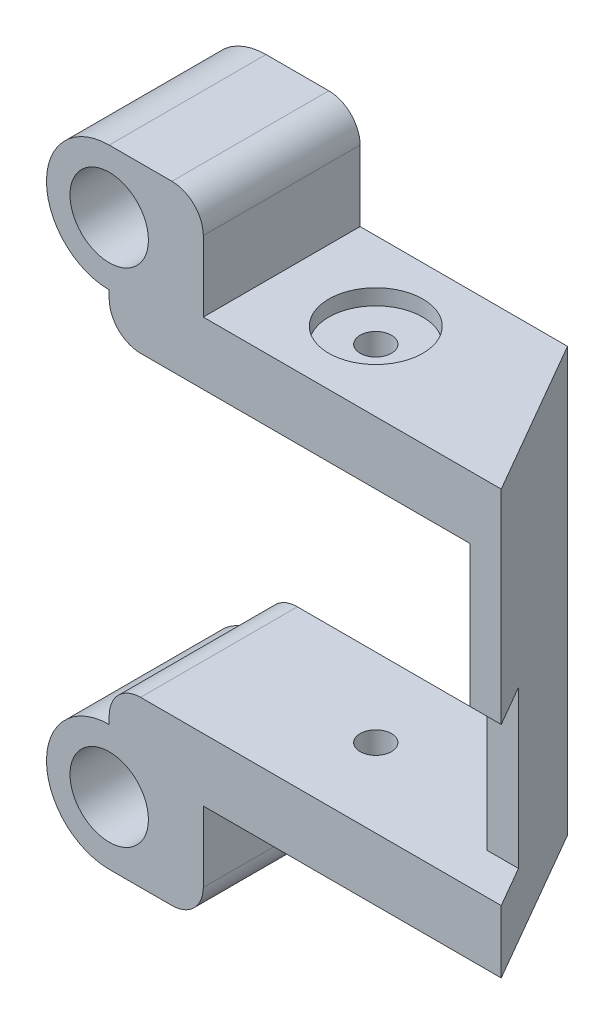
SolidWorks part; units mm, degrees
ref_plane "Alzado" through (0, 0, 0) normal (0, 0, 1) x (1, 0, 0)
ref_plane "Planta" through (0, 0, 0) normal (0, 1, 0) x (1, 0, 0)
ref_plane "Vista lateral" through (0, 0, 0) normal (1, 0, 0) x (0, 0, -1)
sketch "Croquis1" plane through (0, 0, 0) normal (0, 0, 1) x (1, 0, 0)
  line L5 (-106.2316, 22.7007) -> (-131.2316, 22.7007)
  line L6 (-131.2316, 22.7007) -> (-131.2316, 20.2007)
  line L7 (-106.2316, 22.7007) -> (-106.2316, 18.7007)
  line L8 (-106.2316, 18.7007) -> (-125.2316, 18.7007)
  line L9 (-125.2316, 18.7007) -> (-125.2316, 12.2007)
  line L10 (-125.2316, 12.2007) -> (-131.2316, 12.2007)
  circle A0 centre (-131.2316, 16.2007) radius 2.5
  arc A2 (-131.2316, 20.2007) -> (-131.2316, 12.2007) centre (-131.2316, 16.2007) ccw
  dimension "D1" = 4
  dimension "D2" = 5
  dimension "D3" = 6
  dimension "D4" = 6.5
  dimension "D5" = 25
  dimension "D6" = 6.5
  dimension "D7" = 19
  dimension "D8" = 2.5
extrude "Saliente-Extruir1" add sketch "Croquis1" along normal blind 10
sketch "Croquis2" plane through (0, 18.7007, 0) normal (0, -1, 0) x (1, 0, 0)
  line L1 (-106.2316, 0) -> (-106.2316, 10)
  line L2 (-106.2316, 10) -> (-112.0051, 0)
  line L4 (-112.0051, 0) -> (-106.2316, 0)
  line L5 (-125.2316, 10) -> (-125.2316, 0) construction
  line L6 (-106.2316, 10) -> (-106.2316, 0) construction
  circle A0 centre (-119.2316, 5) radius 1
  dimension "D1" = 6
  dimension "D2" = 30
  dimension "D3" = 0
extrude "Cortar-Extruir1" cut sketch "Croquis2" against normal up to vertex (4 mm away) up to point (-106.2316, 22.7007, 10)
sketch "Croquis3" plane through (0, 18.7007, 0) normal (0, -1, 0) x (1, 0, 0)
  line L0 (-106.2316, 10) -> (-108.2316, 10)
  line L1 (-108.2316, 10) -> (-114.0051, 0)
  line L2 (-114.0051, 0) -> (-112.0051, 0)
  line L3 (-106.2316, 10) -> (-112.0051, 0)
  dimension "D1" = 2
  dimension "D2" = 2
extrude "Saliente-Extruir2" add sketch "Croquis3" against normal blind 13.5
sketch "Croquis4" plane through (0, 18.7007, 0) normal (0, -1, 0) x (1, 0, 0)
  circle A0 centre (-119.2316, 5) radius 3
extrude "Cortar-Extruir2" cut sketch "Croquis4" against normal blind 1
fillet "Redondeo1" radius 2 2 edges at (-131.2316, 22.7007, 5) (-125.2316, 12.2007, 5)
mirror "Simetría1" about plane through (0, 32.2007, 0) normal (0, -1, 0) of bodies 104
sketch "Croquis5" plane through (0, 0, 10) normal (0, 0, 1) x (1, 0, 0)
  line L0 (-106.2316, 18.7007) -> (-106.2316, 45.7007) construction
  line L1 (-108.2316, 22.7007) -> (-106.2316, 22.7007)
  line L2 (-108.2316, 22.7007) -> (-108.2316, 32.7007)
  line L3 (-108.2316, 32.7007) -> (-106.2316, 32.7007)
  line L4 (-106.2316, 22.7007) -> (-106.2316, 32.7007)
  dimension "D1" = 10
extrude "Cortar-Extruir3" cut sketch "Croquis5" along direction (-0.5, 0, -0.866) on the side against the normal blind 3
